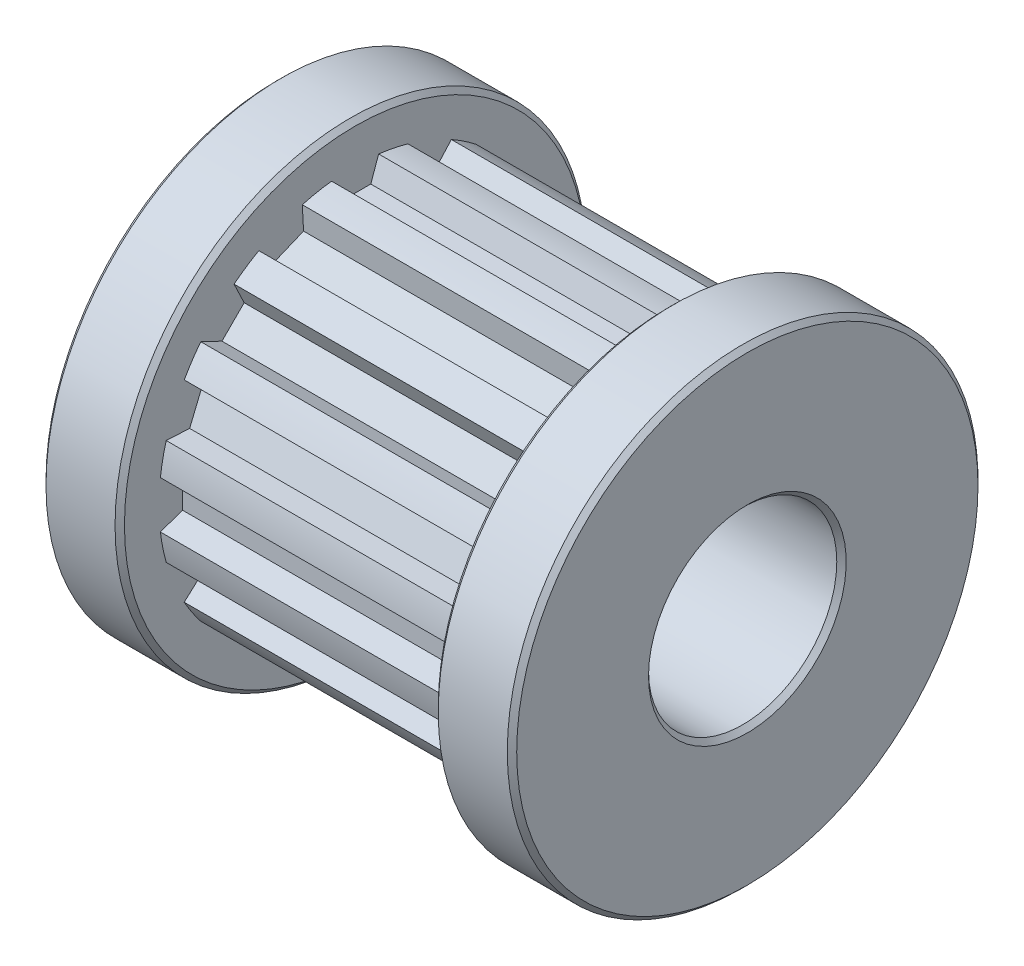
SolidWorks part; units mm, degrees
material "Полиамид П-12Б-20 ТУ 6-05-988-87"
ref_plane "Спереди" through (0, 0, 0) normal (0, 0, 1) x (1, 0, 0)
ref_plane "Сверху" through (0, 0, 0) normal (0, 1, 0) x (1, 0, 0)
ref_plane "Справа" through (0, 0, 0) normal (1, 0, 0) x (0, 0, -1)
ref_axis "ОсьX" through (-88.99, 0, 0) along (1, 0, 0)
ref_axis "ОсьZ" through (0, 55, 0) along (0, -1, 0)
ref_axis "ОсьY" through (0, 0, -88.99) along (0, 0, 1)
sketch "Эскиз1" plane through (0, 0, 0) normal (0, 0, 1) x (1, 0, 0)
  line L0 (-33.311, 0) -> (19.5594, 0) construction
  line L1 (0, 6) -> (0, 15)
  line L2 (0, 15) -> (-5, 15)
  line L3 (-5, 15) -> (-5, 12.5)
  line L4 (-5, 12.5) -> (-25, 12.5)
  line L5 (-25, 12.5) -> (-25, 15)
  line L6 (-25, 15) -> (-30, 15)
  line L7 (-30, 15) -> (-30, 6)
  line L8 (-30, 6) -> (0, 6)
  dimension "D1" = 12
  dimension "D2" = 25
  dimension "D3" = 20
  dimension "D4" = 5
  dimension "D5" = 5
  dimension "D6" = 30
revolve "Повернуть1" add sketch "Эскиз1" angle 360 mid plane about L0
sketch "Эскиз2" plane through (0, 0, 0) normal (0, 1, 0) x (1, 0, 0)
  line L0 (0, -15) -> (0, 15) construction
  circle A0 centre (-12, 0) radius 2.75
  dimension "D1" = 5.5
  dimension "D2" = 12
extrude "Вырез-Вытянуть1" cut sketch "Эскиз2" against normal through all
sketch "Эскиз3" plane through (-5, 0, 0) normal (-1, 0, 0) x (0, 0, 1)
  line L0 (-1.5, 12.4097) -> (-1, 11)
  line L1 (-1, 11) -> (1, 11)
  line L2 (1, 11) -> (1.5, 12.4097)
  circle A0 centre (0, 0) radius 12.5 construction
  arc A1 (1.5, 12.4097) -> (-1.5, 12.4097) centre (0, 0) ccw
  point P7 (0, 11)
  dimension "D1" = 1.5
  dimension "D2" = 2
  dimension "D3" = 3
extrude "Вырез-Вытянуть2" cut sketch "Эскиз3" along normal up to surface (20 mm away) up to face at (-25, 0, 15)
pattern_circular "Круговой массив1" count 16 over 360 about axis through (-33.311, 0, 0) along (-1, 0, 0) of "Вырез-Вытянуть2" reverse direction yes
chamfer "Фаска1" distance 0.3 angle 45 6 edges at (-30, 0, 6) (-30, 0, 15) (-25, 0, 15) (-5, 0, 15) (0, 0, 15) (0, 0, 6)
